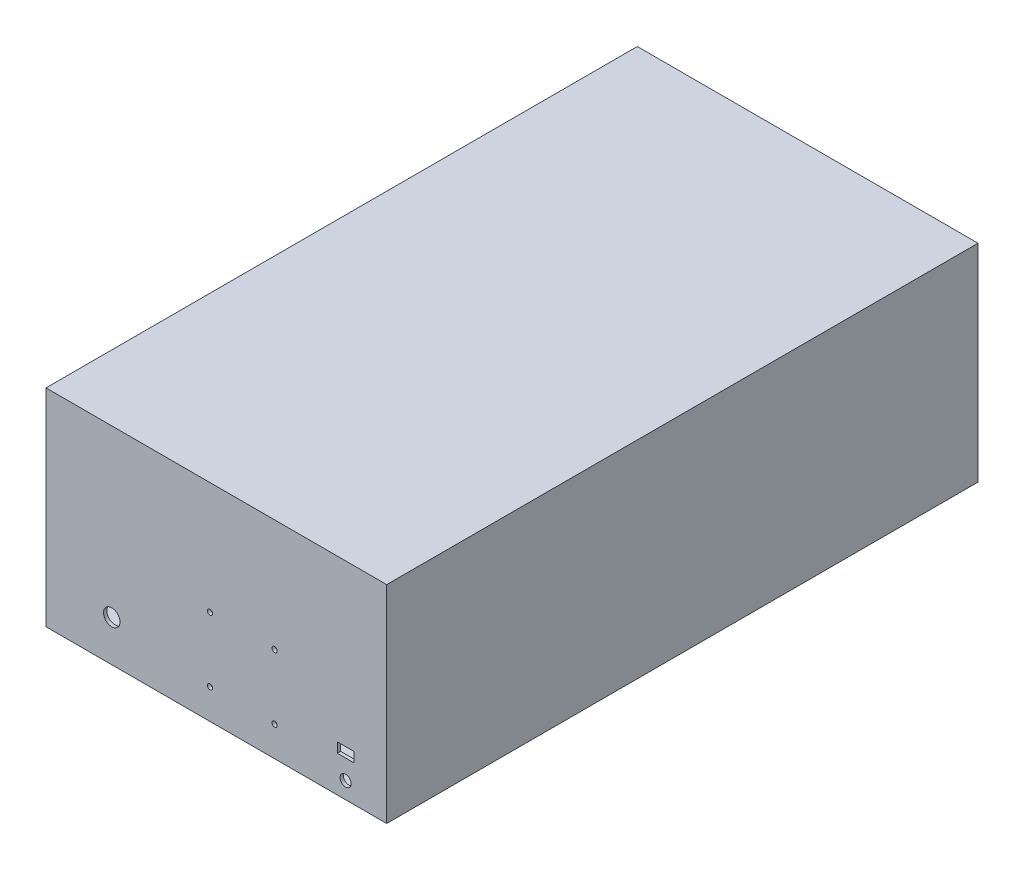
SolidWorks part; units mm, degrees
material "ABS"
ref_plane "Front Plane" through (0, 0, 0) normal (0, 0, 1) x (1, 0, 0)
ref_plane "Top Plane" through (0, 0, 0) normal (0, 1, 0) x (1, 0, 0)
ref_plane "Right Plane" through (0, 0, 0) normal (1, 0, 0) x (0, 0, -1)
sketch "Sketch2" plane through (0, 0, 0) normal (0, 1, 0) x (1, 0, 0)
  line L0 (-103.6, 179.8) -> (-103.6, -179.8)
  line L1 (-101.6, 177.8) -> (101.6, 177.8)
  line L2 (-101.6, 177.8) -> (-101.6, -177.8)
  line L3 (-101.6, -177.8) -> (101.6, -177.8)
  line L4 (101.6, 177.8) -> (101.6, -177.8)
  line L5 (-101.6, 177.8) -> (101.6, -177.8) construction
  line L6 (-101.6, -177.8) -> (101.6, 177.8) construction
  line L7 (-103.6, -179.8) -> (103.6, -179.8)
  line L8 (103.6, 179.8) -> (103.6, -179.8)
  line L9 (-103.6, 179.8) -> (103.6, 179.8)
  point P0 (0, 0)
  dimension "D1" = 355.6
  dimension "D2" = 203.2
  dimension "D3" = 2
extrude "Walls" add sketch "Sketch2" along normal blind 123.825
sketch "Sketch3" plane through (0, 0, 0) normal (0, -1, 0) x (1, 0, 0)
  line L1 (-103.6, -179.8) -> (103.6, -179.8)
  line L2 (-103.6, -179.8) -> (-103.6, 179.8)
  line L3 (-103.6, 179.8) -> (103.6, 179.8)
  line L4 (103.6, -179.8) -> (103.6, 179.8)
  line L5 (-103.6, -179.8) -> (103.6, 179.8) construction
  line L6 (-103.6, 179.8) -> (103.6, -179.8) construction
  point P0 (0, 0)
extrude "Base" add sketch "Sketch3" along normal blind 2
sketch "Sketch4" plane through (0, 0, -179.8) normal (0, 0, -1) x (-1, 0, 0)
  line L0 (103.6, -2) -> (-103.6, -2) construction
  line L3 (103.6, 123.825) -> (103.6, -2) construction
  line L4 (-83.6, 20) -> (-73.6, 20)
  line L5 (-83.6, 20) -> (-83.6, 26)
  line L6 (-83.6, 26) -> (-73.6, 26)
  line L7 (-73.6, 20) -> (-73.6, 26)
  line L8 (-83.6, 20) -> (-73.6, 26) construction
  line L9 (-83.6, 26) -> (-73.6, 20) construction
  line L10 (-103.6, 123.825) -> (-103.6, -2) construction
  circle A1 centre (63.6, 23) radius 5
  point P0 (-78.6, 23)
  dimension "D1" = 25
  dimension "D2" = 10
  dimension "D3" = 25
  dimension "D4" = 6
  dimension "D5" = 40
  dimension "D6" = 10
extrude "Cut-Extrude1" cut sketch "Sketch4" against normal through all
sketch "Sketch5" plane through (0, 0, -179.8) normal (0, 0, -1) x (-1, 0, 0)
  circle A0 centre (-78.6, 8.0963) radius 3.3782 construction
  circle A1 centre (-78.6, 8.0963) radius 3.3782
extrude "Cut-Extrude2" cut sketch "Sketch5" against normal through all
hole_wizard "1/4 Clearance Hole1" positions "Sketch7" profile "Sketch8" hole size "1/4" standard "ANSI Inch" end condition through all
sketch "Sketch7" plane through (0, -2, 0) normal (0, -1, 0) x (-1, 0, 0)
  line L0 (0, 0) -> (-103.6, 0) construction
  line L1 (-103.6, 179.8) -> (-103.6, -179.8) construction
  point P0 (-27, 0)
  point P2 (-5, 0)
  dimension "D1" = 27
  dimension "D2" = 22
sketch "Sketch8" plane through (27, -2, 0) normal (1, 0, 0) x (0, 0, -1)
  line L0 (0, 0) -> (0, 125.825)
  line L1 (0, 125.825) -> (3.3782, 125.825)
  line L2 (3.3782, 125.825) -> (3.3782, 0)
  line L5 (3.3782, 0) -> (0, 0)
  line L11 (0, -6.35) -> (0, 107.95) construction
  dimension "Thru Hole Dia." = 6.7564
  dimension "Thru Hole Depth" = 125.825
sketch "Sketch9" plane through (0, -2, 0) normal (0, -1, 0) x (1, 0, 0)
  circle A0 centre (92, 61.675) radius 1.6
  circle A1 centre (92, -61.675) radius 1.6
  circle A2 centre (49, 61.675) radius 1.6
  circle A3 centre (49, -61.675) radius 1.6
  circle A4 centre (27.1506, -126.7794) radius 1.6
  circle A5 centre (27.1506, -166.0794) radius 1.6
  circle A6 centre (-12.1494, -126.7794) radius 1.6
  circle A7 centre (-12.1494, -166.0794) radius 1.6
  circle A8 centre (23.9728, -62.9055) radius 1.6
  circle A9 centre (23.9728, -83.2055) radius 1.6
  circle A10 centre (3.6728, -62.9055) radius 1.6
  circle A11 centre (3.6728, -83.2055) radius 1.6
  circle A12 centre (-12.7908, 29.5071) radius 1.6
  circle A13 centre (-12.7908, -28.4929) radius 1.6
  circle A14 centre (-61.7908, -28.4929) radius 1.6
  circle A15 centre (-61.7908, 29.5071) radius 1.6
  circle A16 centre (-51.4971, 74.9976) radius 1.6
  circle A17 centre (-12.1971, 74.9976) radius 1.6
  circle A18 centre (-12.1971, 114.2976) radius 1.6
  circle A19 centre (-51.4971, 114.2976) radius 1.6
  dimension "D1" = 3.2
sketch "Sketch10" plane through (0, 0, 179.8) normal (0, 0, 1) x (1, 0, 0)
  circle A0 centre (-3.8836, 55.5451) radius 1.6
  circle A1 centre (35.4164, 55.5451) radius 1.6
  circle A2 centre (35.4164, 16.2451) radius 1.6
  circle A3 centre (-3.8836, 16.2451) radius 1.6
  dimension "D1" = 3.2
extrude "Cut-Extrude3" cut sketch "Sketch9" against normal up to next
extrude "Cut-Extrude4" cut sketch "Sketch10" against normal up to next
sketch "Sketch11" plane through (0, 123.825, 0) normal (0, 1, 0) x (1, 0, 0)
  line L4 (103.6, 179.8) -> (-103.6, 179.8)
  line L5 (-103.6, 179.8) -> (-103.6, -179.8)
  line L6 (-103.6, -179.8) -> (103.6, -179.8)
  line L7 (103.6, -179.8) -> (103.6, 179.8)
  line L8 (103.6, 179.8) -> (-103.6, 179.8)
  line L9 (-103.6, 179.8) -> (-103.6, -179.8)
  line L10 (-103.6, -179.8) -> (103.6, -179.8)
  line L11 (103.6, -179.8) -> (103.6, 179.8)
  dimension "D1" = 0
extrude "Boss-Extrude1" add sketch "Sketch11" against normal blind 10
